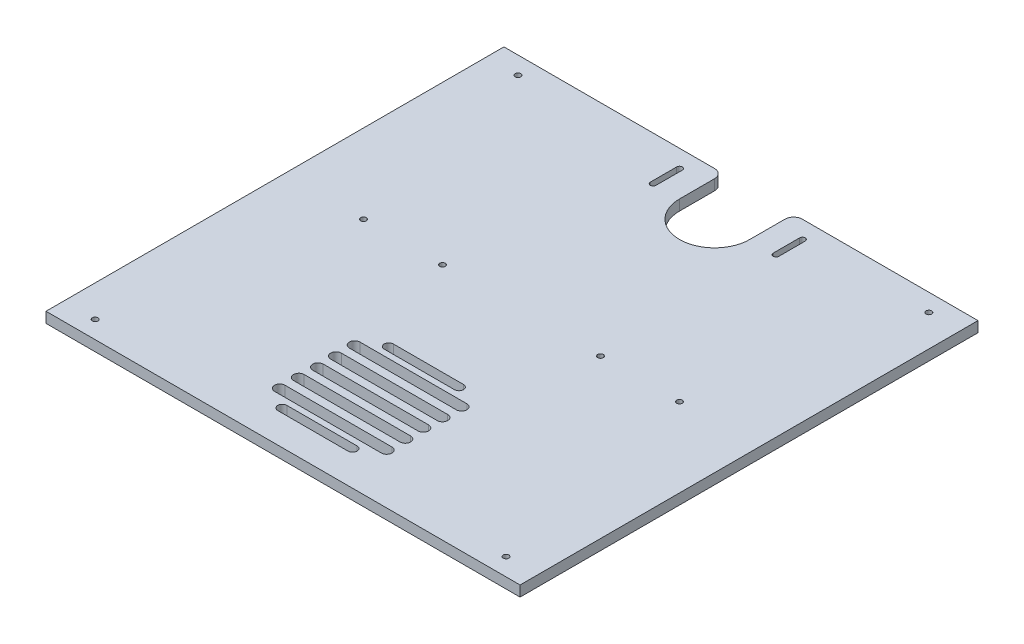
SolidWorks part; units mm, degrees
ref_plane "Front Plane" through (0, 0, 0) normal (0, 0, 1) x (1, 0, 0)
ref_plane "Top Plane" through (0, 0, 0) normal (0, 1, 0) x (1, 0, 0)
ref_plane "Right Plane" through (0, 0, 0) normal (1, 0, 0) x (0, 0, -1)
sketch "Sketch1" plane through (0, 0, 0) normal (0, 1, 0) x (1, 0, 0)
  line L0 (-145, 120) -> (125, 120)
  line L1 (-145, 120) -> (-145, -100.8)
  line L3 (125, 120) -> (125, -100.8)
  line L4 (0, 0) -> (0, 120) construction
  line L7 (-145, -100.8) -> (-145, -140.8)
  line L8 (-145, -140.8) -> (125, -140.8)
  line L9 (125, -100.8) -> (125, -140.8)
  circle A0 centre (-100, -5) radius 1.6
  circle A2 centre (80, -5) radius 1.6
  circle A3 centre (-55, -5) radius 1.6
  circle A4 centre (35, -5) radius 1.6
  circle A6 centre (-55, -5) radius 1.125 construction
  dimension "D1" = 3.2
  dimension "D2" = 40
extrude "Boss-Extrude1" add sketch "Sketch1" along normal blind 6
sketch "Sketch3" plane through (0, 6, 0) normal (0, 1, 0) x (1, 0, 0)
  line L3 (0, 120) -> (0, 0) construction
  line L4 (125, 120) -> (-145, 120) construction
  line L5 (-20, 95) -> (-20, 120)
  line L60 (20, 95) -> (20, 120)
  line L61 (20, 120) -> (-20, 120)
  arc A0 (-20, 95) -> (20, 95) centre (0, 95) ccw
  dimension "D1" = 20
  dimension "D2" = 25
extrude "Cut-Extrude1" cut sketch "Sketch3" against normal through all both and the other way through all
sketch "Sketch4" plane through (0, 0, 0) normal (0, -1, 0) x (1, 0, 0)
  circle A0 centre (107, -110) radius 1.6
  circle A1 centre (-127, -110) radius 1.6
  circle A2 centre (107, 130.8) radius 1.6
  circle A3 centre (-127, 130.8) radius 1.6
extrude "Cut-Extrude2" cut sketch "Sketch4" against normal blind 10
sketch "Sketch5" plane through (0, 6, 0) normal (0, 1, 0) x (1, 0, 0)
  line L0 (20, 95) -> (20, 120) construction
  line L1 (-20, 120) -> (-20, 95) construction
  line L2 (20, 95) -> (20, 120) construction
  line L3 (-20, 120) -> (-20, 95) construction
  line L4 (-20, 120) -> (20, 120) construction
  line L5 (-35, 120) -> (-35, 95) construction
  line L6 (-20, 120) -> (-145, 120) construction
  line L7 (-35, 110) -> (-35, 95) construction
  line L8 (-33.4, 110) -> (-33.4, 95)
  line L9 (-36.6, 110) -> (-36.6, 95)
  line L10 (0, 120) -> (0, 95) construction
  line L11 (35, 120) -> (35, 95) construction
  line L12 (35, 110) -> (35, 95) construction
  line L13 (33.4, 110) -> (33.4, 95)
  line L14 (36.6, 110) -> (36.6, 95)
  arc A0 (-33.4, 110) -> (-36.6, 110) centre (-35, 110) ccw
  arc A1 (-36.6, 95) -> (-33.4, 95) centre (-35, 95) ccw
  arc A2 (33.4, 110) -> (36.6, 110) centre (35, 110) cw
  arc A3 (36.6, 95) -> (33.4, 95) centre (35, 95) cw
  point P8 (-35, 110)
  point P12 (-35, 102.5)
  point P21 (35, 102.5)
  dimension "D3" = 1.6
  dimension "D2" = 10
extrude "Cut-Extrude3" cut sketch "Sketch5" against normal blind 10
fillet "Fillet1" radius 5 2 edges at (20, 3, -120) (-20, 3, -120)
sketch "Sketch6" plane through (0, 0, 0) normal (0, -1, 0) x (1, 0, 0)
  line L0 (10, 58.0215) -> (-30, 58.0215) construction
  line L1 (-30, 63.1632) -> (10, 63.1632) construction
  line L2 (20.436, 66.5711) -> (-40.436, 66.5711) construction
  line L3 (-40.436, 72.5711) -> (20.436, 72.5711) construction
  line L4 (20.3168, 77.3259) -> (-40.3168, 77.3259) construction
  line L5 (-40.3168, 83.3259) -> (20.3168, 83.3259) construction
  line L6 (-30, 123.7773) -> (10, 123.7773) construction
  line L7 (10, 118.6356) -> (-30, 118.6356) construction
  line L8 (-40.436, 115.2277) -> (20.436, 115.2277) construction
  line L9 (20.436, 109.2277) -> (-40.436, 109.2277) construction
  line L10 (-40.3168, 104.4728) -> (20.3168, 104.4728) construction
  line L11 (20.3168, 98.4728) -> (-40.3168, 98.4728) construction
  line L12 (20, 87.8994) -> (-40, 87.8994) construction
  line L13 (-40, 93.8994) -> (20, 93.8994) construction
  line L14 (10, 58.0215) -> (-30, 58.0215)
  line L15 (-30, 63.1632) -> (10, 63.1632)
  line L16 (20.436, 66.5711) -> (-40.436, 66.5711)
  line L17 (-40.436, 72.5711) -> (20.436, 72.5711)
  line L18 (20.3168, 77.3259) -> (-40.3168, 77.3259)
  line L19 (-40.3168, 83.3259) -> (20.3168, 83.3259)
  line L20 (-30, 123.7773) -> (10, 123.7773)
  line L21 (10, 118.6356) -> (-30, 118.6356)
  line L22 (-40.436, 115.2277) -> (20.436, 115.2277)
  line L23 (20.436, 109.2277) -> (-40.436, 109.2277)
  line L24 (-40.3168, 104.4728) -> (20.3168, 104.4728)
  line L25 (20.3168, 98.4728) -> (-40.3168, 98.4728)
  line L26 (20, 87.8994) -> (-40, 87.8994)
  line L27 (-40, 93.8994) -> (20, 93.8994)
  arc A0 (-30, 63.1632) -> (-30, 58.0215) centre (-30, 60.5923) ccw construction
  arc A1 (10, 58.0215) -> (10, 63.1632) centre (10, 60.5923) ccw construction
  arc A2 (-40.436, 72.5711) -> (-40.436, 66.5711) centre (-40.436, 69.5711) ccw construction
  arc A3 (20.436, 66.5711) -> (20.436, 72.5711) centre (20.436, 69.5711) ccw construction
  arc A4 (-40.3168, 83.3259) -> (-40.3168, 77.3259) centre (-40.3168, 80.3259) ccw construction
  arc A5 (20.3168, 77.3259) -> (20.3168, 83.3259) centre (20.3168, 80.3259) ccw construction
  arc A6 (-30, 123.7773) -> (-30, 118.6356) centre (-30, 121.2064) ccw construction
  arc A7 (10, 118.6356) -> (10, 123.7773) centre (10, 121.2064) ccw construction
  arc A8 (20.436, 109.2277) -> (20.436, 115.2277) centre (20.436, 112.2277) ccw construction
  arc A9 (-40.436, 115.2277) -> (-40.436, 109.2277) centre (-40.436, 112.2277) ccw construction
  arc A10 (-40.3168, 104.4728) -> (-40.3168, 98.4728) centre (-40.3168, 101.4728) ccw construction
  arc A11 (20.3168, 98.4728) -> (20.3168, 104.4728) centre (20.3168, 101.4728) ccw construction
  arc A12 (-40, 93.8994) -> (-40, 87.8994) centre (-40, 90.8994) ccw construction
  arc A13 (20, 87.8994) -> (20, 93.8994) centre (20, 90.8994) ccw construction
  arc A14 (-30, 63.1632) -> (-30, 58.0215) centre (-30, 60.5923) ccw
  arc A15 (10, 58.0215) -> (10, 63.1632) centre (10, 60.5923) ccw
  arc A16 (-40.436, 72.5711) -> (-40.436, 66.5711) centre (-40.436, 69.5711) ccw
  arc A17 (20.436, 66.5711) -> (20.436, 72.5711) centre (20.436, 69.5711) ccw
  arc A18 (-40.3168, 83.3259) -> (-40.3168, 77.3259) centre (-40.3168, 80.3259) ccw
  arc A19 (20.3168, 77.3259) -> (20.3168, 83.3259) centre (20.3168, 80.3259) ccw
  arc A20 (-30, 123.7773) -> (-30, 118.6356) centre (-30, 121.2064) ccw
  arc A21 (10, 118.6356) -> (10, 123.7773) centre (10, 121.2064) ccw
  arc A22 (20.436, 109.2277) -> (20.436, 115.2277) centre (20.436, 112.2277) ccw
  arc A23 (-40.436, 115.2277) -> (-40.436, 109.2277) centre (-40.436, 112.2277) ccw
  arc A24 (-40.3168, 104.4728) -> (-40.3168, 98.4728) centre (-40.3168, 101.4728) ccw
  arc A25 (20.3168, 98.4728) -> (20.3168, 104.4728) centre (20.3168, 101.4728) ccw
  arc A26 (-40, 93.8994) -> (-40, 87.8994) centre (-40, 90.8994) ccw
  arc A27 (20, 87.8994) -> (20, 93.8994) centre (20, 90.8994) ccw
extrude "Cut-Extrude4" cut sketch "Sketch6" against normal blind 10 and the other way blind 10
